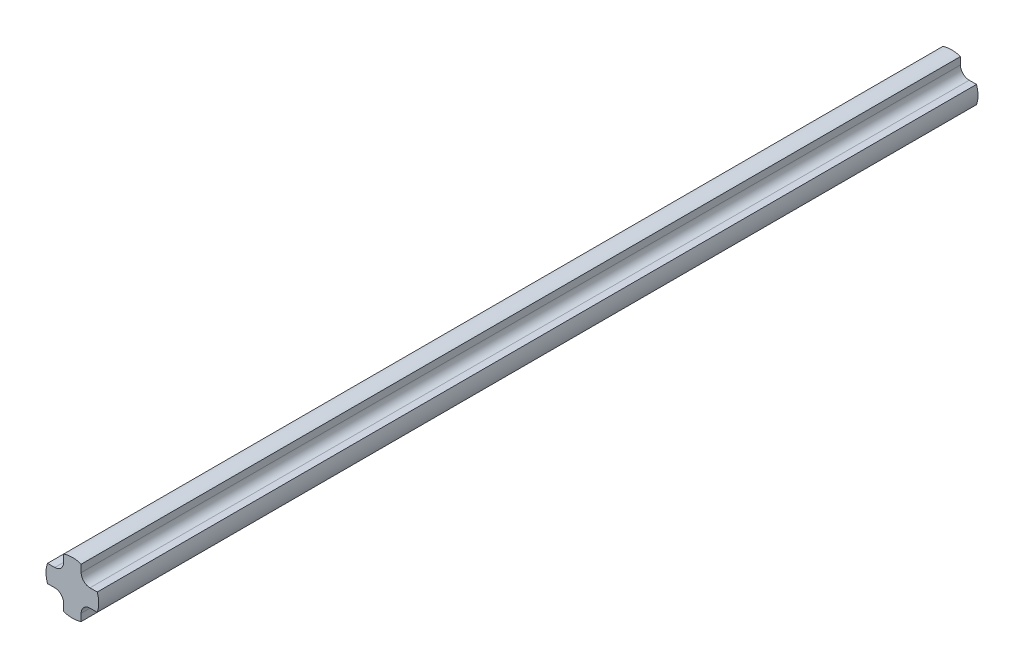
SolidWorks part; units mm, degrees
ref_plane "Front Plane" through (0, 0, 0) normal (1, 0, 0) x (0, 1, 0)
ref_plane "Top Plane" through (0, 0, 0) normal (0, 0, 1) x (0, 1, 0)
ref_plane "Right Plane" through (0, 0, 0) normal (0, 1, 0) x (-1, 0, 0)
sketch "Sketch1" plane through (0, 0, 0) normal (0, 0, 1) x (0, 1, 0)
  line L1 (-50, 141.4214) -> (-50, 0)
  line L2 (50, 141.4214) -> (50, 0)
  line L3 (-50, 0) -> (50, 0)
  arc A0 (50, 141.4214) -> (-50, 141.4214) centre (0, 0) ccw
  point P3 (0, 0)
  dimension "D1" = 150
  dimension "D2" = 100
extrude "Boss-Extrude1" add sketch "Sketch1" along normal blind 5000
ref_axis "Axis1" through (0, 0, -10) along (0, 0, 1)
pattern_circular "CirPattern1" count 4 over 360 about axis through (0, 0, -10) along (0, 0, 1) of bodies 101
combine bodies "Combine1" bodies to combine 101 102 103 104
fillet "Fillet1" radius 50 4 edges at (50, 50, 2500) (50, -50, 2500) (-50, 50, 2500) (-50, -50, 2500)
